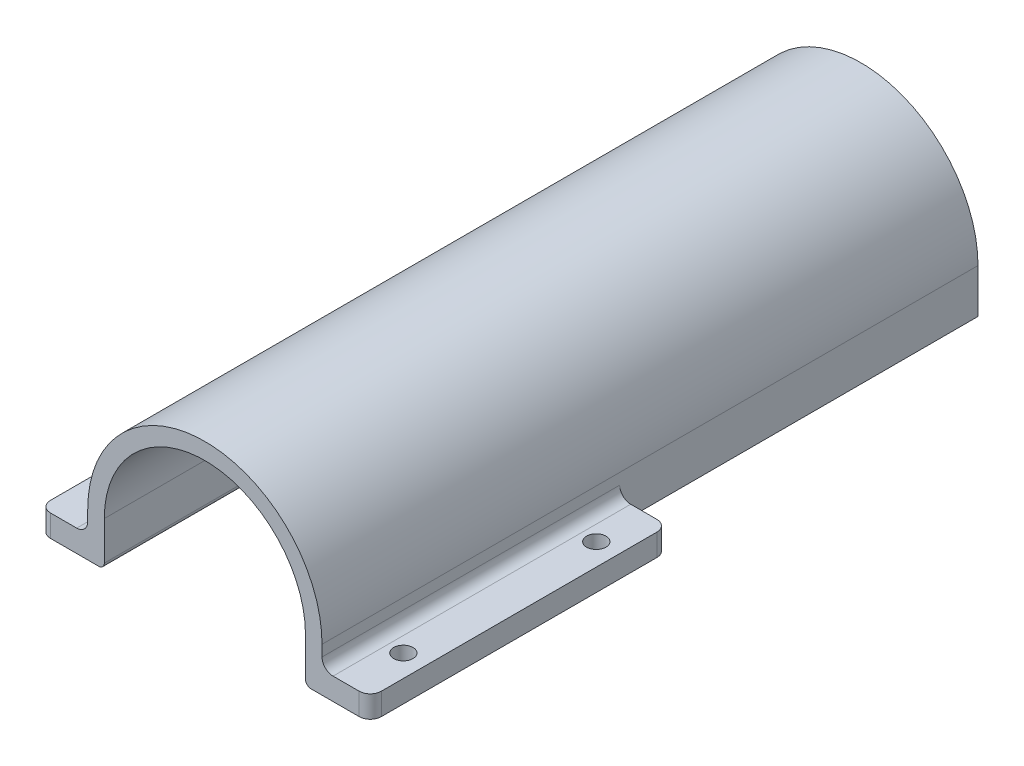
SolidWorks part; units mm, degrees
ref_plane "前视基准面" through (0, 0, 0) normal (0, 0, 1) x (1, 0, 0)
ref_plane "上视基准面" through (0, 0, 0) normal (0, 1, 0) x (1, 0, 0)
ref_plane "右视基准面" through (0, 0, 0) normal (1, 0, 0) x (0, 0, -1)
other "Configuration Table"
sketch "草图11" plane through (0, 0, 0) normal (0, 0, 1) x (1, 0, 0)
  line L0 (-30, 0) -> (-30, 4)
  line L1 (-30, 0) -> (-18.25, 0)
  line L2 (30, 0) -> (18.25, 0)
  line L3 (-21.25, 8) -> (-21.25, 6)
  line L4 (-21.25, 6) -> (-18.25, 6)
  line L5 (0, 2) -> (0, 11.182) construction
  line L6 (-18.25, 8) -> (-18.25, 0)
  line L7 (-30, 4) -> (-23.25, 4)
  line L8 (21.25, 6) -> (18.25, 6)
  line L9 (18.25, 8) -> (18.25, 0)
  line L10 (21.25, 8) -> (21.25, 6)
  line L11 (30, 4) -> (23.25, 4)
  line L12 (30, 0) -> (30, 4)
  arc A0 (18.25, 8) -> (-18.25, 8) centre (0, 8) ccw
  arc A1 (21.25, 8) -> (-21.25, 8) centre (0, 8) ccw
  arc A3 (-23.25, 4) -> (-21.25, 6) centre (-23.25, 6) ccw
  arc A5 (23.25, 4) -> (21.25, 6) centre (23.25, 6) cw
  dimension "D1" = 18.25
  dimension "D4" = 2
  dimension "D2" = 21.25
  dimension "D3" = 8
  dimension "D5" = 8
  dimension "D6" = 30
  dimension "D7" = 4
extrude "凸台-拉伸5" add sketch "草图11" along normal blind 54 contours A3 L7 L0 L1 L6 L4 | A0 L5 A1 L3 L4 L6 | L5 A0 L9 L8 L10 A1 | L11 A5 L8 L9 L2 L12
sketch "草图10" plane through (0, 0, 0) normal (0, 1, 0) x (1, 0, 0)
  line L0 (-30, -2) -> (-30, -52)
  line L1 (-30, 1) -> (30, 1) construction
  line L4 (30, -2) -> (30, -52)
  line L5 (-28, -54) -> (28, -54)
  line L6 (-28, 0) -> (28, 0)
  arc A0 (30, -52) -> (28, -54) centre (28, -52) cw
  arc A1 (-28, -54) -> (-30, -52) centre (-28, -52) cw
  arc A2 (30, -2) -> (28, 0) centre (28, -2) ccw
  arc A3 (-28, 0) -> (-30, -2) centre (-28, -2) ccw
  circle A4 centre (-26, -9) radius 1.75
  circle A5 centre (26, -9) radius 1.75
  circle A6 centre (26, -44) radius 1.75
  circle A7 centre (-26, -44) radius 1.75
  dimension "D1" = 2
  dimension "D3" = 2
  dimension "D4" = 3.5
  dimension "D2" = 54
  dimension "D7" = 9
  dimension "D8" = 10
  dimension "D5" = 2
  dimension "D6" = 2
extrude "切除-拉伸1" cut sketch "草图10" along normal up to next (26.25 mm away) flip side to cut
fillet "圆角1" radius 1 2 edges at (18.25, 0, 27) (-18.25, 0, 27)
sketch "草图12" plane through (0, 0, 0) normal (0, 0, -1) x (-1, 0, 0)
  line L2 (18.25, 8) -> (18.25, 1) construction
  line L3 (-18.25, 8) -> (-18.25, 1) construction
  line L4 (18.25, 8) -> (18.25, 1)
  line L5 (-18.25, 8) -> (-18.25, 1)
  line L6 (-19.25, 0) -> (-21.25, 0)
  line L7 (-28, 0) -> (-19.25, 0) construction
  line L8 (-21.25, 0) -> (-21.25, 6)
  line L9 (21.25, 6) -> (21.25, 0)
  line L10 (-28, 0) -> (-19.25, 0)
  line L11 (-18.25, 1) -> (-18.25, 8)
  line L12 (18.25, 8) -> (18.25, 1)
  line L13 (19.25, 0) -> (28, 0)
  line L14 (28, 0) -> (28, 4)
  line L15 (28, 4) -> (23.25, 4)
  line L16 (21.25, 6) -> (21.25, 8)
  line L17 (-21.25, 8) -> (-21.25, 6)
  line L18 (-23.25, 4) -> (-28, 4)
  line L19 (-28, 4) -> (-28, 0)
  line L21 (-18.25, 6) -> (-18.25, 8)
  line L22 (18.25, 8) -> (18.25, 6)
  line L26 (21.25, 6) -> (21.25, 8)
  line L27 (-21.25, 8) -> (-21.25, 6)
  line L30 (28, 0) -> (19.25, 0) construction
  line L31 (21.25, 0) -> (19.25, 0)
  arc A0 (18.25, 1) -> (19.25, 0) centre (19.25, 1) ccw construction
  arc A1 (-19.25, 0) -> (-18.25, 1) centre (-19.25, 1) ccw construction
  arc A2 (18.25, 1) -> (19.25, 0) centre (19.25, 1) ccw
  arc A3 (-19.25, 0) -> (-18.25, 1) centre (-19.25, 1) ccw
  arc A6 (-19.25, 0) -> (-18.25, 1) centre (-19.25, 1) ccw
  arc A7 (18.25, 8) -> (-18.25, 8) centre (0, 8) ccw
  arc A8 (18.25, 1) -> (19.25, 0) centre (19.25, 1) ccw
  arc A9 (21.25, 6) -> (23.25, 4) centre (23.25, 6) ccw
  arc A10 (21.25, 8) -> (-21.25, 8) centre (0, 8) ccw
  arc A11 (-23.25, 4) -> (-21.25, 6) centre (-23.25, 6) ccw
  arc A13 (18.25, 8) -> (-18.25, 8) centre (0, 8) ccw
  arc A16 (21.25, 8) -> (-21.25, 8) centre (0, 8) ccw
  line M17 (-28, 0) -> (-19.25, 0)
  arc M18 (-19.25, 0) -> (-18.25, 1) centre (-19.25, 1) ccw
  line M19 (-18.25, 1) -> (-18.25, 8)
  arc M20 (-18.25, 8) -> (18.25, 8) centre (0, 8) cw
  line M21 (18.25, 8) -> (18.25, 1)
  arc M22 (18.25, 1) -> (19.25, 0) centre (19.25, 1) ccw
  line M23 (19.25, 0) -> (28, 0)
  line M27 (21.25, 6) -> (21.25, 8)
  arc M28 (21.25, 8) -> (-21.25, 8) centre (0, 8) ccw
  line M29 (-21.25, 8) -> (-21.25, 6)
  dimension "D1" = 0
extrude "凸台-拉伸6" add sketch "草图12" along normal blind 65 contours L9 L8 L5 L4 M27 M28 M29 M17 M18 M19 M20 M21 M22 M23 region at (0, 26.7659, 0)
sketch "草图13" plane through (0, 0, -65) normal (0, 0, -1) x (-1, 0, 0)
  line L4 (-18.25, 1) -> (18.25, 1)
  line L5 (18.25, 1) -> (18.25, 8)
  line L6 (-18.25, 8) -> (-18.25, 1)
  arc A2 (18.25, 8) -> (-18.25, 8) centre (0, 8) ccw construction
  arc A3 (18.25, 8) -> (-18.25, 8) centre (0, 8) ccw
  arc A4 (18.25, 1) -> (19.25, 0) centre (19.25, 1) ccw construction
  line M24 (-18.25, 1) -> (-18.25, 8)
  arc M25 (-18.25, 8) -> (18.25, 8) centre (0, 8) cw
  line M26 (18.25, 8) -> (18.25, 1)
extrude "凸台-拉伸7" add sketch "草图13" against normal blind 2 contours L4 M24 M26 M25 region at (0, 12.0556, -65)
